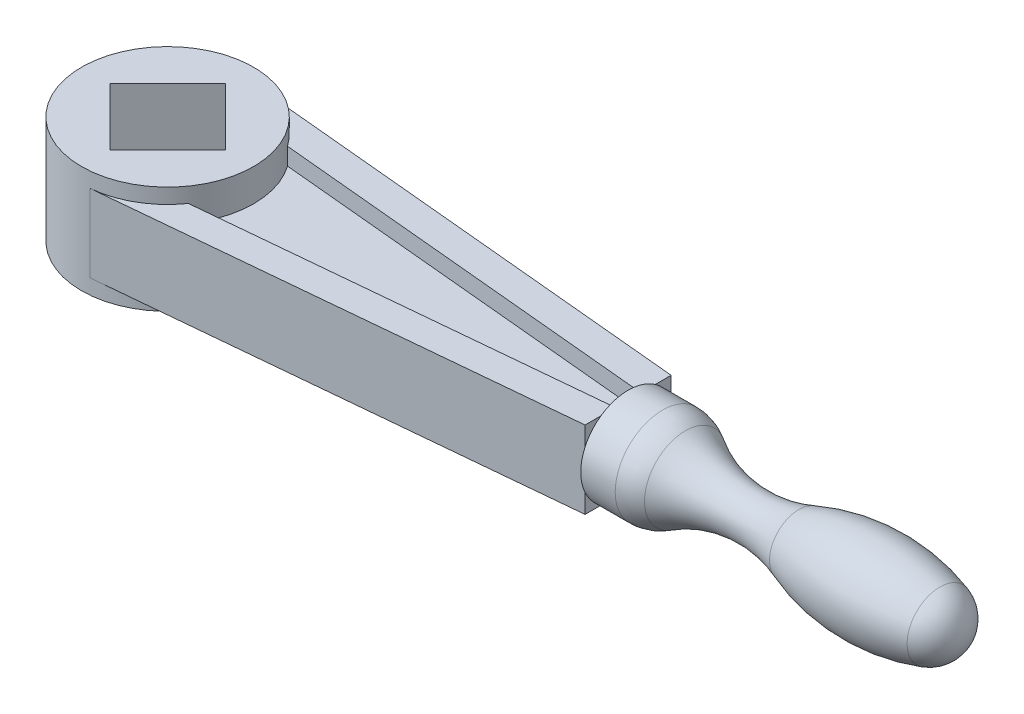
SolidWorks part; units mm, degrees
ref_plane "前视基准面" through (0, 0, 0) normal (0, 0, 1) x (1, 0, 0)
ref_plane "上视基准面" through (0, 0, 0) normal (0, 1, 0) x (1, 0, 0)
ref_plane "右视基准面" through (0, 0, 0) normal (1, 0, 0) x (0, 0, -1)
other "Configuration Table"
sketch "草图1" plane through (0, 0, 0) normal (0, 1, 0) x (1, 0, 0)
  line L1 (0, 13.435) -> (13.435, 0)
  line L2 (0, 13.435) -> (-13.435, 0)
  line L3 (-13.435, 0) -> (0, -13.435)
  line L4 (13.435, 0) -> (0, -13.435)
  line L5 (0, 13.435) -> (0, -13.435) construction
  line L6 (-13.435, 0) -> (13.435, 0) construction
  circle A0 centre (0, 0) radius 20
  point P7 (0, 0)
  dimension "D1" = 40
  dimension "D2" = 19
extrude "凸台-拉伸1" add sketch "草图1" along normal mid plane 25
sketch "草图2" plane through (0, 0, 0) normal (0, 1, 0) x (1, 0, 0)
  line L0 (0, 0) -> (107, 0) construction
  line L1 (107, -10) -> (107, 10)
  line L2 (107, 10) -> (1.8774, 19.9117)
  line L3 (107, -10) -> (1.8774, -19.9117)
  circle A0 centre (0, 0) radius 20 construction
  arc A1 (1.8774, -19.9117) -> (1.8774, 19.9117) centre (0, 0) ccw
  circle A3 centre (0, 0) radius 20
  arc A4 (1.8774, -19.9117) -> (1.8774, 19.9117) centre (0, 0) ccw
  dimension "D2" = 107
  dimension "D3" = 20
  dimension "D1" = 0
extrude "凸台-拉伸2" add sketch "草图2" along normal mid plane 18 contours A4 L0 L1 L2 | L0 A1 L3 L1 region at (56.9876, 0, -7.6376) region at (56.9876, 0, 7.6376)
sketch "草图3" plane through (0, 0, 0) normal (0, 1, 0) x (1, 0, 0)
  line L2 (106.3429, 3.0309) -> (1.2203, 12.9426)
  line L3 (107, 2.969) -> (16.3519, 11.5159)
  line L4 (107, -10) -> (107, 10) construction
  line L5 (106.3429, -3.0309) -> (1.2203, -12.9426)
  line L6 (107, -2.969) -> (16.3519, -11.5159)
  line L7 (107, -2.969) -> (107, 2.969)
  arc A0 (1.8774, -19.9117) -> (1.8774, 19.9117) centre (0, 0) ccw construction
  arc A1 (16.3519, -11.5159) -> (16.3519, 11.5159) centre (0, 0) ccw
  point P4 (107, 2.969)
  point P9 (114.4842, 2.2633)
  point P11 (117.1175, -2.015)
  point P16 (107, 2.969)
  point P17 (107, -2.969)
  point P18 (107, 2.969)
  point P19 (0, 0)
  dimension "D1" = 7
  dimension "D2" = 7
extrude "切除-拉伸1" cut sketch "草图3" against normal blind 4 from vertex starting at point (107, 9, 10)
extrude "切除-拉伸2" cut sketch "草图3<2>" along normal blind 4 from vertex starting at point (107, -9, 10)
sketch "草图3<2>" plane through (0, 0, 0) normal (0, 1, 0) x (1, 0, 0) same geometry as "草图3"
sketch "草图4" plane through (0, 0, 0) normal (0, 1, 0) x (1, 0, 0)
  line L0 (0, 0) -> (285.9566, 0) construction
  line L1 (107, 0) -> (107, 11)
  line L2 (107, 11) -> (115, 11)
  line L3 (107, 2.969) -> (107, 10) construction
  line L4 (107, 0) -> (185, 0)
  arc A0 (115, 11) -> (120.2944, 9.4835) centre (115, 1) cw
  arc A1 (120.2944, 9.4835) -> (146.6836, 6.8337) centre (136.1776, 34.9339) ccw
  arc A2 (146.6836, 6.8337) -> (179.4393, 7.619) centre (164.1938, -40) cw
  arc A3 (179.4393, 7.619) -> (185, 0) centre (177, 0) cw
  point P16 (0, 0)
  point P17 (0, 0)
  dimension "D2" = 30
  dimension "D3" = 50
  dimension "D4" = 8
  dimension "D5" = 20
  dimension "D8" = 10
  dimension "D6" = 78
  dimension "D1" = 22
  dimension "D7" = 8
revolve "旋转1" add sketch "草图4" angle 360 about L0
